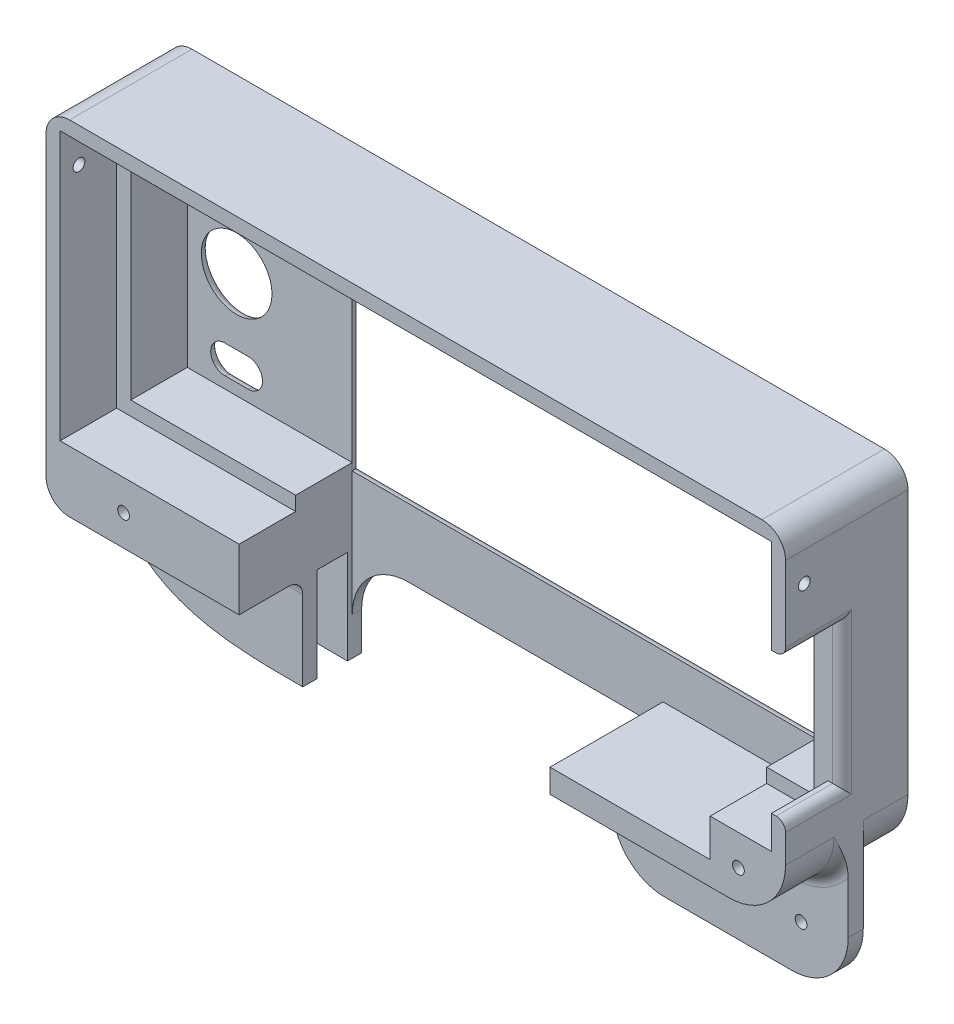
SolidWorks part; units mm, degrees
material "ABS generico"
ref_plane "Piano frontale" through (0, 0, 0) normal (0, 0, 1) x (1, 0, 0)
ref_plane "Piano superiore" through (0, 0, 0) normal (0, 1, 0) x (1, 0, 0)
ref_plane "Piano destro" through (0, 0, 0) normal (1, 0, 0) x (0, 0, -1)
sketch "Schizzo1" plane through (0, 0, 0) normal (0, 0, 1) x (1, 0, 0)
  line L1 (75.5, -28.5) -> (-75.5, -28.5)
  line L2 (75.5, -28.5) -> (75.5, 28.5)
  line L3 (75.5, 28.5) -> (-75.5, 28.5)
  line L4 (-75.5, -28.5) -> (-75.5, 28.5)
  line L5 (75.5, -28.5) -> (-75.5, 28.5) construction
  line L6 (75.5, 28.5) -> (-75.5, -28.5) construction
  point P0 (0, 0)
  dimension "D1" = 151
  dimension "D2" = 57
extrude "Estrusione-Sottile1" add sketch "Schizzo1" along normal blind 12 thin thin type one direction wall 3
sketch "Schizzo2" plane through (0, 0, 0) normal (0, 0, 1) x (1, 0, 0)
  line L0 (-72.5, 25.5) -> (-72.5, -25.5)
  line L1 (-75.5, 28.5) -> (75.5, 28.5) construction
  line L2 (-75.5, 28.5) -> (-75.5, -28.5) construction
  line L3 (-75.5, -28.5) -> (75.5, -28.5) construction
  line L4 (75.5, 28.5) -> (75.5, -28.5) construction
  line L5 (-72.5, -25.5) -> (72.5, -25.5)
  line L6 (72.5, 25.5) -> (72.5, -25.5)
  line L7 (-72.5, 25.5) -> (72.5, 25.5)
  line L8 (78.5, 31.5) -> (-78.5, 31.5) construction
  line L9 (78.5, -31.5) -> (78.5, 31.5) construction
  line L10 (-78.5, -31.5) -> (78.5, -31.5) construction
  line L11 (-78.5, 31.5) -> (-78.5, -31.5) construction
  line L12 (78.5, 31.5) -> (-78.5, 31.5)
  line L13 (78.5, -31.5) -> (78.5, 31.5)
  line L14 (-78.5, -31.5) -> (78.5, -31.5)
  line L15 (-78.5, 31.5) -> (-78.5, -31.5)
  dimension "D1" = 3
extrude "Estrusione-Estrusione1" add sketch "Schizzo2" against normal blind 12
sketch "Schizzo3" plane through (0, 0, -12) normal (0, 0, -1) x (-1, 0, 0)
  line L1 (-78.5, 31.5) -> (78.5, 31.5)
  line L2 (-78.5, 31.5) -> (-78.5, -31.5)
  line L3 (-78.5, -31.5) -> (78.5, -31.5)
  line L4 (78.5, 31.5) -> (78.5, -31.5)
extrude "Estrusione-Estrusione2" add sketch "Schizzo3" along normal blind 2
sketch "Schizzo4" plane through (0, 0, 12) normal (0, 0, 1) x (1, 0, 0)
  line L0 (-75.5, -24.8554) -> (-75.5, -56.5339) construction
  line L1 (-75.5, 28.5) -> (-75.5, -28.5) construction
  line L2 (-37.5, -24.8554) -> (-37.5, -56.5339) construction
  line L3 (17.2201, 25.5) -> (101.3711, 25.5) construction
  line L4 (72.5, 25.5) -> (-72.5, 25.5) construction
  line L5 (-37.5, -36.5) -> (62.5, -36.5)
  line L6 (17.2201, -36.5) -> (101.3711, -36.5) construction
  line L7 (62.5, -24.8554) -> (62.5, -36.5)
  line L8 (-37.5, -36.5) -> (-37.5, -25.5)
  line L9 (62.5, -24.8554) -> (62.5, -56.5339) construction
  line L10 (-72.5, -25.5) -> (72.5, -25.5) construction
  line L11 (-37.5, -25.5) -> (62.5, -25.5)
  line M2 (-78.5, -31.5) -> (78.5, -31.5)
  line M5 (75.5, -28.5) -> (-75.5, -28.5)
  dimension "D1" = 38
  dimension "D2" = 62
  dimension "D3" = 100
extrude "Taglio-Estrusione1" cut sketch "Schizzo4" against normal up to surface (24 mm away) contours L8 L5 L7 M2 | L8 L7 M2 M5 | L11 L8 L7 M5 up to face at (0, 0, -12)
sketch "Schizzo5" plane through (0, 0, -14) normal (0, 0, -1) x (-1, 0, 0)
  line L0 (-62.4991, 14.967) -> (-62.4991, -27.033)
  line L1 (-61.4991, 13.967) -> (36.4992, 13.967) construction
  line L2 (-61.4991, 13.967) -> (-61.4991, -26.033) construction
  line L3 (-61.4991, -26.033) -> (36.4992, -26.033) construction
  line L4 (36.4992, 13.967) -> (36.4992, -26.033) construction
  line L5 (-62.4991, -27.033) -> (37.4992, -27.033)
  line L6 (37.4992, 14.967) -> (37.4992, -27.033)
  line L7 (-62.4991, 14.967) -> (37.4992, 14.967)
  dimension "D1" = 1
extrude "Taglio-Estrusione2" cut sketch "Schizzo5" against normal blind 10
sketch "Schizzo6" plane through (0, 0, -14) normal (0, 0, -1) x (-1, 0, 0)
  circle A0 centre (62.0323, -3.033) radius 6.5 construction
  circle A1 centre (62.0323, -3.033) radius 7.5
  dimension "D2" = 15
  dimension "D1" = 1
extrude "Taglio-Estrusione3" cut sketch "Schizzo6" against normal blind 10
sketch "Schizzo7" plane through (0, 0, 12) normal (0, 0, 1) x (1, 0, 0)
  line L0 (69.5973, 28.5) -> (97.0664, 28.5) construction
  line L1 (75.5, 28.5) -> (-75.5, 28.5) construction
  line L2 (69.5973, 8.5) -> (97.0664, 8.5) construction
  line L3 (69.5973, -21.5) -> (97.0664, -21.5) construction
  line L4 (75.5, -28.5) -> (75.5, 28.5) construction
  line L5 (75.5, 8.5) -> (80.4219, 8.5)
  line L6 (75.5, 8.5) -> (75.5, -21.5)
  line L7 (75.5, -21.5) -> (80.4219, -21.5)
  line L8 (80.4219, 8.5) -> (80.4219, -21.5)
  dimension "D1" = 20
  dimension "D2" = 30
extrude "Taglio-Estrusione4" cut sketch "Schizzo7" against normal up to surface (12 mm away) up to face at (4.1667, -9, 0)
sketch "Schizzo8" plane through (0, -31.5, 0) normal (0, -1, 0) x (1, 0, 0)
  line L8 (62.5, 12) -> (62.5, -12)
  line L9 (62.5, -12) -> (-37.5, -12)
  line L10 (-37.5, -12) -> (-37.5, 12)
  line L11 (-37.5, 12) -> (-78.5, 12)
  line L12 (-78.5, 12) -> (-78.5, -14)
  line L13 (-78.5, -14) -> (78.5, -14)
  line L14 (78.5, -14) -> (78.5, 12)
  line L15 (78.5, 12) -> (62.5, 12)
  line L16 (62.5, 12) -> (62.5, -12)
  line L17 (62.5, -12) -> (-37.5, -12)
  line L18 (-37.5, -12) -> (-37.5, 12)
  line L19 (-37.5, 12) -> (-78.5, 12)
  line L20 (-78.5, 12) -> (-78.5, -14)
  line L21 (-78.5, -14) -> (78.5, -14)
  line L22 (78.5, -14) -> (78.5, 12)
  line L23 (78.5, 12) -> (62.5, 12)
  dimension "D1" = 0
extrude "Estrusione-Estrusione3" add sketch "Schizzo8" along normal blind 30
sketch "Schizzo10" plane through (78.5, 0, 0) normal (1, 0, 0) x (0, 0, -1)
  line L1 (14, -61.5) -> (8, -61.5)
  line L2 (14, -61.5) -> (14, -41.5)
  line L3 (14, -41.5) -> (8, -41.5)
  line L4 (8, -61.5) -> (8, -41.5)
  dimension "D1" = 6
  dimension "D2" = 20
sketch "Schizzo15" plane through (-37.5, 0, 0) normal (1, 0, 0) x (0, 0, -1)
  line L2 (-12, -36.5) -> (-12, -41.5)
  line L3 (-12, -41.5) -> (-0.2, -41.5)
  line L6 (12, -25.5) -> (12, -61.5) construction
  line L7 (-0.2, -41.5) -> (12, -41.5)
  line L9 (-12, -36.5) -> (12, -36.5)
  line L10 (12, -41.5) -> (12, -36.5)
  dimension "D2" = 5
extrude "Estrusione-Estrusione6" add sketch "Schizzo15" along normal up to surface (100 mm away) up to face at (62.5, -38.5, 0)
sketch "Schizzo18" plane through (0, 0, 12) normal (0, 0, 1) x (1, 0, 0)
  line L17 (-37.5, -41.5) -> (62.5, -41.5)
  line L18 (78.5, -61.5) -> (78.5, -21.5)
  line L19 (78.5, -21.5) -> (75.5, -21.5)
  line L20 (75.5, -21.5) -> (75.5, -28.5)
  line L21 (75.5, -28.5) -> (62.5, -28.5)
  line L22 (62.5, -28.5) -> (62.5, -36.5)
  line L23 (62.5, -36.5) -> (-37.5, -36.5)
  line L24 (-37.5, -36.5) -> (-37.5, -28.5)
  line L25 (-37.5, -28.5) -> (-75.5, -28.5)
  line L26 (-75.5, -28.5) -> (-75.5, 28.5)
  line L27 (-75.5, 28.5) -> (75.5, 28.5)
  line L28 (75.5, 28.5) -> (75.5, 8.5)
  line L29 (75.5, 8.5) -> (78.5, 8.5)
  line L30 (78.5, 8.5) -> (78.5, 31.5)
  line L31 (78.5, 31.5) -> (-78.5, 31.5)
  line L32 (-78.5, 31.5) -> (-78.5, -61.5)
  line L33 (-37.5, -41.5) -> (62.5, -41.5)
  line L34 (78.5, -61.5) -> (78.5, -21.5)
  line L35 (78.5, -21.5) -> (75.5, -21.5)
  line L36 (75.5, -21.5) -> (75.5, -28.5)
  line L37 (75.5, -28.5) -> (62.5, -28.5)
  line L38 (62.5, -28.5) -> (62.5, -36.5)
  line L39 (62.5, -36.5) -> (-37.5, -36.5)
  line L40 (-37.5, -36.5) -> (-37.5, -28.5)
  line L41 (-37.5, -28.5) -> (-75.5, -28.5)
  line L42 (-75.5, -28.5) -> (-75.5, 28.5)
  line L43 (-75.5, 28.5) -> (75.5, 28.5)
  line L44 (75.5, 28.5) -> (75.5, 8.5)
  line L45 (75.5, 8.5) -> (78.5, 8.5)
  line L46 (78.5, 8.5) -> (78.5, 31.5)
  line L47 (78.5, 31.5) -> (-78.5, 31.5)
  line L48 (-78.5, 31.5) -> (-78.5, -61.5)
  line L53 (-78.5, -61.5) -> (-37.5, -61.5)
  line L54 (-78.5, -61.5) -> (-37.5, -61.5)
  line L55 (-37.5, -61.5) -> (-37.5, -41.5)
  line L56 (-37.5, -61.5) -> (-37.5, -41.5)
  line L57 (62.5, -41.5) -> (62.5, -61.5)
  line L58 (62.5, -41.5) -> (62.5, -61.5)
  line L59 (62.5, -61.5) -> (78.5, -61.5)
  line L60 (62.5, -61.5) -> (78.5, -61.5)
  dimension "D1" = 0
sketch "Schizzo19" plane through (-78.5, 0, 0) normal (-1, 0, 0) x (0, 0, 1)
  circle A0 centre (8, 20.25) radius 1.25
extrude "Taglio-Estrusione8" cut sketch "Schizzo19" against normal blind 186
sketch "Schizzo20" plane through (78.5, 0, 0) normal (1, 0, 0) x (0, 0, -1)
  line L0 (0.8, -61.5) -> (0.8, -41.5)
  line L4 (11, -61.5) -> (11, -41.5)
  line L5 (0.8, -41.5) -> (11, -41.5)
  line L6 (0.8, -61.5) -> (11, -61.5)
  dimension "D1" = 20
  dimension "D2" = 10.2
extrude "Taglio-Estrusione9" cut sketch "Schizzo20" against normal blind 186
sketch "Schizzo22" plane through (78.5, 0, 0) normal (1, 0, 0) x (0, 0, -1)
  line L0 (0.8, -61.5) -> (-12, -61.5) construction
  line L1 (-12, -61.5) -> (-4, -61.5)
  line L2 (-12, -61.5) -> (-12, -41.5)
  line L3 (-12, -41.5) -> (-4, -41.5)
  line L4 (-4, -61.5) -> (-4, -41.5)
  line L5 (-12, -61.5) -> (-12, -21.5) construction
  line L6 (0.8, -41.5) -> (-12, -41.5) construction
  dimension "D1" = 8
extrude "Taglio-Estrusione10" cut sketch "Schizzo22" against normal blind 186
sketch "Schizzo23" plane through (62.5, 0, 0) normal (-1, 0, 0) x (0, 0, 1)
  line L0 (-11, -61.5) -> (-11, -41.5) construction
  line L1 (-12, -41.5) -> (-11, -41.5)
  line L2 (-12, -41.5) -> (-12, -61.5)
  line L3 (-12, -61.5) -> (-11, -61.5)
  line L4 (-11, -41.5) -> (-11, -61.5)
  line L5 (4, -41.5) -> (-0.8, -41.5) construction
  line L6 (-0.8, -41.5) -> (4, -41.5)
  line L7 (-0.8, -41.5) -> (-0.8, -61.5)
  line L8 (-0.8, -61.5) -> (4, -61.5)
  line L9 (4, -41.5) -> (4, -61.5)
  line L10 (4, -61.5) -> (4, -41.5) construction
extrude "Estrusione-Estrusione7" add sketch "Schizzo23" along normal blind 34
sketch "Schizzo24" plane through (-37.5, 0, 0) normal (1, 0, 0) x (0, 0, -1)
  line L0 (11, -61.5) -> (11, -41.5) construction
  line L1 (11, -41.5) -> (14, -41.5)
  line L2 (11, -41.5) -> (11, -61.5)
  line L3 (11, -61.5) -> (14, -61.5)
  line L4 (14, -41.5) -> (14, -61.5)
  line L5 (11, -41.5) -> (12, -41.5) construction
  line L6 (14, 31.5) -> (14, -61.5) construction
extrude "Taglio-Estrusione11" cut sketch "Schizzo24" along normal blind 168
sketch "Schizzo25" plane through (-78.5, 0, 0) normal (-1, 0, 0) x (0, 0, 1)
  line L0 (4, -61.5) -> (4, -41.5) construction
  line L1 (-14, -61.5) -> (4, -61.5)
  line L2 (-14, -61.5) -> (-14, -51.5)
  line L3 (-14, -51.5) -> (4, -51.5)
  line L4 (4, -61.5) -> (4, -51.5)
  dimension "D1" = 10
sketch "Schizzo26" plane through (-78.5, 0, 0) normal (-1, 0, 0) x (0, 0, 1)
  line L0 (4, -41.5) -> (-0.8, -41.5) construction
  line L1 (-0.8, -41.5) -> (4, -41.5)
  line L2 (-0.8, -41.5) -> (-0.8, -51.5)
  line L3 (-0.8, -51.5) -> (4, -51.5)
  line L4 (4, -41.5) -> (4, -51.5)
  line L5 (-0.8, -41.5) -> (-0.8, -61.5) construction
  line L6 (4, -61.5) -> (4, -41.5) construction
sketch "Schizzo27" plane through (-78.5, 0, 0) normal (-1, 0, 0) x (0, 0, 1)
  line L0 (4, -41.5) -> (-0.8, -41.5) construction
  line L1 (-0.8, -41.5) -> (4, -41.5)
  line L2 (-0.8, -41.5) -> (-0.8, -61.5)
  line L3 (-0.8, -61.5) -> (4, -61.5)
  line L4 (4, -41.5) -> (4, -61.5)
  line L5 (-11, -41.5) -> (-0.8, -41.5) construction
  line L6 (4, -61.5) -> (-0.8, -61.5) construction
  line L7 (4, -61.5) -> (4, -41.5) construction
extrude "Taglio-Estrusione14" cut sketch "Schizzo27" against normal blind 68
sketch "Schizzo28" plane through (0, -41.5, 0) normal (0, -1, 0) x (1, 0, 0)
  line L0 (-37.5, -14) -> (-37.5, -11) construction
  line L1 (-37.5, -12) -> (28.5, -12)
  line L2 (-37.5, -12) -> (-37.5, 12)
  line L3 (-37.5, 12) -> (28.5, 12)
  line L5 (62.5, -12) -> (-37.5, -12) construction
  line L6 (78.5, 12) -> (78.5, -29.6704) construction
  line L7 (78.5, 12) -> (-78.5, 12) construction
  line L8 (28.5, 12) -> (28.5, -12)
  line L9 (28.5, 12) -> (28.5, -29.6704) construction
  dimension "D1" = 50
extrude "Taglio-Estrusione15" cut sketch "Schizzo28" against normal blind 20
sketch "Schizzo29" plane through (0, 0, -14) normal (0, 0, -1) x (-1, 0, 0)
  line L0 (59.5323, -20.033) -> (64.5323, -20.033) construction
  line L1 (59.5323, -17.033) -> (64.5323, -17.033)
  line L2 (59.5323, -23.033) -> (64.5323, -23.033)
  arc A0 (59.5323, -17.033) -> (59.5323, -23.033) centre (59.5323, -20.033) ccw
  arc A1 (64.5323, -23.033) -> (64.5323, -17.033) centre (64.5323, -20.033) ccw
  point P2 (62.0323, -20.033)
  dimension "D1" = 6
  dimension "D2" = 5
extrude "Taglio-Estrusione16" cut sketch "Schizzo29" against normal blind 5
fillet "Raccordo1" radius 2 9 edges at (-67.5323, -20.033, -14) (-62.0323, -23.033, -14) (-56.5323, -20.033, -14) (12.5, -27.033, -14) (62.4991, -6.033, -14) (12.5, 14.967, -14) (-37.4992, -6.033, -14) (-62.0323, -17.033, -14) (-69.5323, -3.033, -14)
fillet "Raccordo2" radius 12 3 edges at (78.5, -41.5, -7.4) (78.5, -41.5, 8) (-37.5, -41.5, -13)
fillet "Raccordo3" radius 5 2 edges at (-78.5, 31.5, -1) (78.5, 31.5, -1)
fillet "Raccordo4" radius 5 1 edges at (-78.5, -41.5, 0.5)
sketch "Schizzo30" plane through (0, 0, -14) normal (0, 0, -1) x (-1, 0, 0)
  line L1 (78.5, -61.5) -> (78.5, 26.5) construction
  line L2 (78.5, 14.065) -> (78.5, -66.5698) construction
  line L3 (78.5, -36.5) -> (109.3666, -36.5) construction
  line L4 (78.5, -13.6711) -> (78.5, -41.162) construction
  line L5 (37.5, -53.5) -> (37.5, -73.8619) construction
  line L6 (37.5, -61.5) -> (37.5, -53.5) construction
  line L7 (37.5, -61.5) -> (24.7541, -70.657)
  line L8 (24.7541, -70.657) -> (58.2904, -78.6268)
  line L9 (58.2904, -78.6268) -> (100.5066, -61.5)
  line L10 (100.5066, -61.5) -> (100.5066, -60.9512)
  line L11 (78.5, -36.5) -> (100.5066, -60.9512)
  arc A0 (73.5, -41.5) -> (78.5, -36.5) centre (73.5, -36.5) ccw construction
  spline S0 degree 3 poles (37.5, -61.5) (48.258, -61.2094) (78.5, -63.8701) (78.5, -36.5) knots 0 0 0 0 1 1 1 1
extrude "Taglio-Estrusione18" cut sketch "Schizzo30" against normal blind 5
fillet "Raccordo6" radius 2 3 edges at (78.5, -21.5, 6) (78.5, -6.5, 0) (78.5, 8.5, 6)
sketch "Schizzo31" plane through (0, 0, -0.8) normal (0, 0, -1) x (-1, 0, 0)
  line L0 (-49.4026, -41.5) -> (-91.6131, -41.5) construction
  line L1 (-66.5, -41.5) -> (25.5, -41.5) construction
  line L2 (-38.5, -51.6) -> (-91.6131, -51.6) construction
  line L3 (-78.5, -44.0174) -> (-78.5, -80.0577) construction
  line L4 (-78.5, -29.5) -> (-78.5, -61.5) construction
  line L5 (-68.5, -44.0174) -> (-68.5, -80.0577) construction
  line L6 (-38.5, -44.0174) -> (-38.5, -80.0577) construction
  line L7 (-49.4026, -51.6) -> (-91.6131, -51.6) construction
  circle A0 centre (-68.5, -51.6) radius 1.25
  circle A1 centre (-38.5, -51.6) radius 1.25
  circle A2 centre (-48.5, -51.6) radius 1.25
  dimension "D4" = 2.5
  dimension "D5" = 2.5
  dimension "D6" = 2.5
  dimension "D7" = 20
  dimension "D1" = 10.1
  dimension "D2" = 10
  dimension "D3" = 40
extrude "Taglio-Estrusione19" cut sketch "Schizzo31" against normal blind 5
fillet "Raccordo7" radius 12 1 edges at (78.5, -61.5, 1.6)
sketch "Schizzo32" plane through (0, 0, -0.8) normal (0, 0, -1) x (-1, 0, 0)
  line L0 (-78.5, -49.5) -> (-78.5, -41.5)
  line L5 (-78.5, -29.5) -> (-78.5, -49.5)
  line L6 (-66.5, -61.5) -> (-28.5, -61.5)
  line L7 (-28.5, -61.5) -> (-28.5, -41.5)
  line L9 (-28.5, -41.5) -> (-66.5, -41.5)
  line L11 (-66.5, -61.5) -> (-28.5, -61.5)
  line L12 (-28.5, -61.5) -> (-28.5, -41.5)
  line L14 (-28.5, -41.5) -> (-78.5, -41.5)
  arc A2 (-78.5, -49.5) -> (-66.5, -61.5) centre (-66.5, -49.5) ccw
  arc A3 (-78.5, -29.5) -> (-66.5, -41.5) centre (-66.5, -29.5) ccw
  arc A4 (-78.5, -49.5) -> (-66.5, -61.5) centre (-66.5, -49.5) ccw
  dimension "D1" = 0
fillet "Raccordo8" radius 11 1 edges at (28.5, -61.5, 1.6)
sketch "Schizzo33" plane through (0, 0, 12) normal (0, 0, 1) x (1, 0, 0)
  line L0 (-37.5, -35) -> (-76.5171, -35) construction
  line L1 (-37.5, -41.5) -> (-37.5, -28.5) construction
  line L2 (-37.5, -35) -> (105.1703, -35) construction
  line L3 (-62.0323, -10.533) -> (-62.0323, -63.6008) construction
  line L4 (68.5, -52.85) -> (68.5, -6.9456) construction
  circle A0 centre (-62.0323, -3.033) radius 7.5 construction
  circle A1 centre (68.5, -51.6) radius 1.25 construction
  circle A2 centre (-62.0323, -35) radius 1.25
  circle A3 centre (68.5, -35) radius 1.25
  dimension "D1" = 2.5
  dimension "D2" = 2.5
extrude "Taglio-Estrusione20" cut sketch "Schizzo33" against normal blind 10
sketch "Schizzo34" plane through (0, 0, -0.8) normal (0, 0, -1) x (-1, 0, 0)
  line L4 (-66.5, -61.5) -> (-39.5, -61.5)
  line L5 (-28.5, -50.5) -> (-28.5, -41.5)
  line L6 (-28.5, -41.5) -> (-66.5, -41.5)
  line L7 (-78.5, -29.5) -> (-78.5, -49.5)
  line L8 (-66.5, -61.5) -> (-39.5, -61.5)
  line L9 (-28.5, -50.5) -> (-28.5, -41.5)
  line L10 (-28.5, -41.5) -> (-66.5, -41.5)
  line L11 (-78.5, -29.5) -> (-78.5, -49.5)
  circle A0 centre (-68.5, -51.6) radius 1.25
  circle A1 centre (-48.5, -51.6) radius 1.25
  circle A2 centre (-38.5, -51.6) radius 1.25
  arc A3 (-39.5, -61.5) -> (-28.5, -50.5) centre (-39.5, -50.5) ccw
  arc A4 (-78.5, -29.5) -> (-66.5, -41.5) centre (-66.5, -29.5) ccw
  arc A5 (-78.5, -49.5) -> (-66.5, -61.5) centre (-66.5, -49.5) ccw
  arc A6 (-39.5, -61.5) -> (-28.5, -50.5) centre (-39.5, -50.5) ccw
  arc A7 (-78.5, -29.5) -> (-66.5, -41.5) centre (-66.5, -29.5) ccw
  arc A8 (-78.5, -49.5) -> (-66.5, -61.5) centre (-66.5, -49.5) ccw
  dimension "D1" = 0
extrude "Estrusione-Estrusione8" add sketch "Schizzo34" along normal blind 3.7
ref_plane "Piano1" through (0, 0, -5) normal (0, 0, 1) x (1, 0, 0)
sketch "Schizzo35" plane through (0, 0, -4.5) normal (0, 0, -1) x (-1, 0, 0)
  line L2 (37.5, -41.5) -> (37.5, -61.5)
  line L3 (73.5, -41.5) -> (37.5, -41.5)
  line L4 (37.5, -41.5) -> (37.5, -61.5)
  line L5 (73.5, -41.5) -> (37.5, -41.5)
  arc A1 (73.5, -41.5) -> (78.5, -36.5) centre (73.5, -36.5) ccw
  arc A2 (73.5, -41.5) -> (78.5, -36.5) centre (73.5, -36.5) ccw
  spline S1 degree 3 poles (2658.2102, -1521.0101) (-2688.9033, 1566.649) (2654.5751, -1878.0549) (-2148.9152, 1965.8681) knots -3.447389 -3.447389 -3.447389 -3.447389 4.035817 4.035817 4.035817 4.035817 only from (37.5, -61.5) to (78.5, -36.5)
  spline S2 degree 3 poles (37.5, -61.5) (48.258, -61.2094) (78.5, -63.8701) (78.5, -36.5) knots 0 0 0 0 1 1 1 1
  dimension "D1" = 0
extrude "Estrusione-Estrusione9" add sketch "Schizzo35" against normal blind 3
sketch "Schizzo36" plane through (0, 0, 4) normal (0, 0, 1) x (1, 0, 0)
  line L4 (28.5, -41.5) -> (28.5, -50.5)
  line L5 (39.5, -61.5) -> (66.5, -61.5)
  line L6 (78.5, -49.5) -> (78.5, -29.5)
  line L7 (66.5, -41.5) -> (28.5, -41.5)
  line L8 (28.5, -41.5) -> (28.5, -50.5)
  line L9 (39.5, -61.5) -> (66.5, -61.5)
  line L10 (78.5, -49.5) -> (78.5, -29.5)
  line L11 (66.5, -41.5) -> (28.5, -41.5)
  arc A3 (28.5, -50.5) -> (39.5, -61.5) centre (39.5, -50.5) ccw
  arc A4 (66.5, -61.5) -> (78.5, -49.5) centre (66.5, -49.5) ccw
  arc A5 (66.5, -41.5) -> (78.5, -29.5) centre (66.5, -29.5) ccw
  arc A6 (28.5, -50.5) -> (39.5, -61.5) centre (39.5, -50.5) ccw
  arc A7 (66.5, -61.5) -> (78.5, -49.5) centre (66.5, -49.5) ccw
  arc A8 (66.5, -41.5) -> (78.5, -29.5) centre (66.5, -29.5) ccw
  dimension "D1" = 0
extrude "Taglio-Estrusione21" cut sketch "Schizzo36" against normal blind 5.3
fillet "Raccordo9" radius 3 4 edges at (-77.0355, -40.0355, -1.5) (-55.5, -41.5, -1.5) (47.5, -41.5, -1.3) (74.9853, -37.9853, -1.3)
